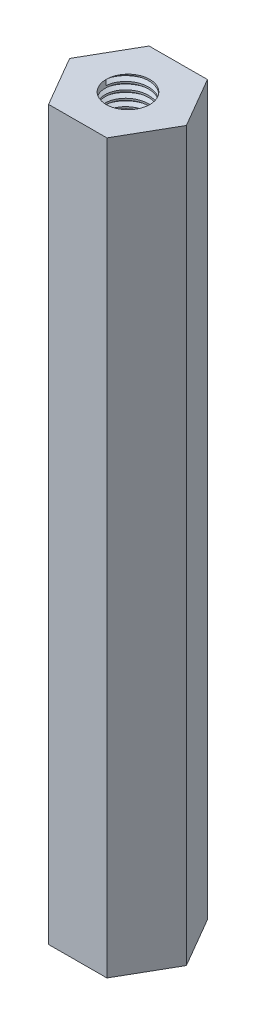
SolidWorks part; units mm, degrees
ref_plane "前视基准面" through (0, 0, 0) normal (0, 0, 1) x (1, 0, 0)
ref_plane "上视基准面" through (0, 0, 0) normal (0, 1, 0) x (1, 0, 0)
ref_plane "右视基准面" through (0, 0, 0) normal (1, 0, 0) x (0, 0, -1)
sketch "草图1" plane through (0, 0, 0) normal (0, 1, 0) x (1, 0, 0)
  line L1 (2.0098, -3.4584) -> (4, 0.0114)
  line L2 (4, 0.0114) -> (1.9902, 3.4698)
  line L3 (1.9902, 3.4698) -> (-2.0098, 3.4584)
  line L4 (-2.0098, 3.4584) -> (-4, -0.0114)
  line L5 (-4, -0.0114) -> (-1.9902, -3.4698)
  line L6 (-1.9902, -3.4698) -> (2.0098, -3.4584)
  circle A0 centre (0, 0) radius 3.4641 construction
  dimension "D1" = 4
extrude "凸台-拉伸1" add sketch "草图1" along normal blind 50
sketch "草图2" plane through (0, 0, 0) normal (0, -1, 0) x (1, 0, 0)
  circle A0 centre (0, 0) radius 1.5
  dimension "D1" = 3
extrude "切除-拉伸1" cut sketch "草图2" against normal blind 10
sketch "草图3" plane through (0, 50, 0) normal (0, 1, 0) x (1, 0, 0)
  circle A0 centre (0, 0) radius 1.5
  dimension "D1" = 3
extrude "切除-拉伸2" cut sketch "草图3" against normal blind 10
thread "螺纹线1" pitch 0.5 method cut profile "螺纹线轮廓1" start angle 0, offset 0, length 8, pitch 0.5, diameter 3
ref_plane "基准面1" through (1.5, 0, 0) normal (0, 0, 1) x (1, 0, 0)
sketch "螺纹线轮廓1" plane through (1.5, 0, 0) normal (0, 0, 1) x (1, 0, 0)
  line L0 (0, 0) -> (0, 0.5) construction
  line L1 (0, 0) -> (0.2706, 0.1562)
  line L2 (0.2706, 0.1562) -> (0.2706, 0.2187)
  line L3 (0.2706, 0.2187) -> (0, 0.375)
  line L4 (0.2706, 0.1875) -> (0, 0.1875) construction
  line L11 (0, 0) -> (0, 0.375)
  point P2 (0, 0)
  dimension "Pitch" = 0.5
  dimension "Profile_Angle" = 60
  dimension "Profile_Land" = 0.0625
  dimension "Profile_Height" = 0.2706
thread "螺纹线2" pitch 0.5 method cut profile "螺纹线轮廓2" start angle 0, offset 0, length 8, pitch 0.5, diameter 3
ref_plane "基准面2" through (-1.5, 50, 0) normal (0, 0, 1) x (-1, 0, 0)
sketch "螺纹线轮廓2" plane through (-1.5, 50, 0) normal (0, 0, 1) x (-1, 0, 0)
  line L0 (0, 0) -> (0, 0.5) construction
  line L1 (0, 0) -> (0.2706, 0.1562)
  line L2 (0.2706, 0.1562) -> (0.2706, 0.2187)
  line L3 (0.2706, 0.2187) -> (0, 0.375)
  line L4 (0.2706, 0.1875) -> (0, 0.1875) construction
  line L11 (0, 0) -> (0, 0.375)
  point P2 (0, 0)
  dimension "Pitch" = 0.5
  dimension "Profile_Angle" = 60
  dimension "Profile_Land" = 0.0625
  dimension "Profile_Height" = 0.2706
